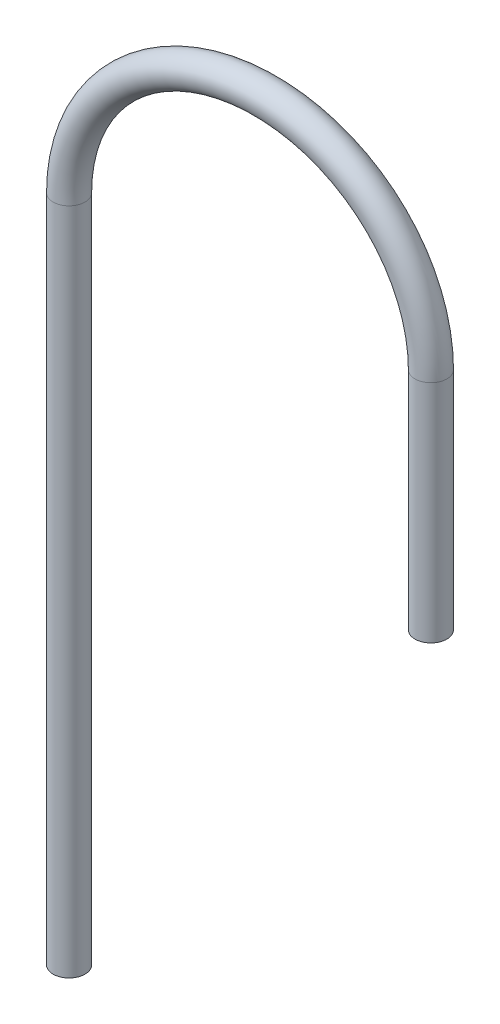
SolidWorks part; units mm, degrees
material "PE faible/moyenne densité"
ref_plane "Front" through (0, 0, 0) normal (0, 0, 1) x (1, 0, 0)
ref_plane "Top" through (0, 0, 0) normal (0, 1, 0) x (1, 0, 0)
ref_plane "Right" through (0, 0, 0) normal (1, 0, 0) x (0, 0, -1)
sketch3d "Esquisse3D1"
  line L0 (-14, 165, -59.25) -> (-14, 207.375, -59.25)
  line L1 (-76.8149, 207.375, -54.0281) -> (-76.8149, 81.65, -54.0281)
  arc A0 (-14, 207.375, -59.25) -> (-76.8149, 207.375, -54.0281) centre (-45.4075, 207.375, -56.6391) ccw
  circle A1 centre (-76.8149, 89.65, -54.0281) radius 1.1 construction
  point P3 (-42.7965, 207.375, -25.2316)
  point P10 (-76.8149, 88.55, -54.0281)
  dimension "D5" = 125.725
  dimension "D4" = 31.5158
  dimension "D1" = 165
  dimension "D2" = 59.25
  dimension "D3" = 14
  dimension "D6" = 81.65
sweep "Balayage-Mince1" add path "Esquisse3D1" circular profile diameter 6 parameters "D1"=1, "D3"=6
equation "\"D5@Esquisse3D1\"=140-((\"D6@Esquisse3D1\"-81)/2)"
